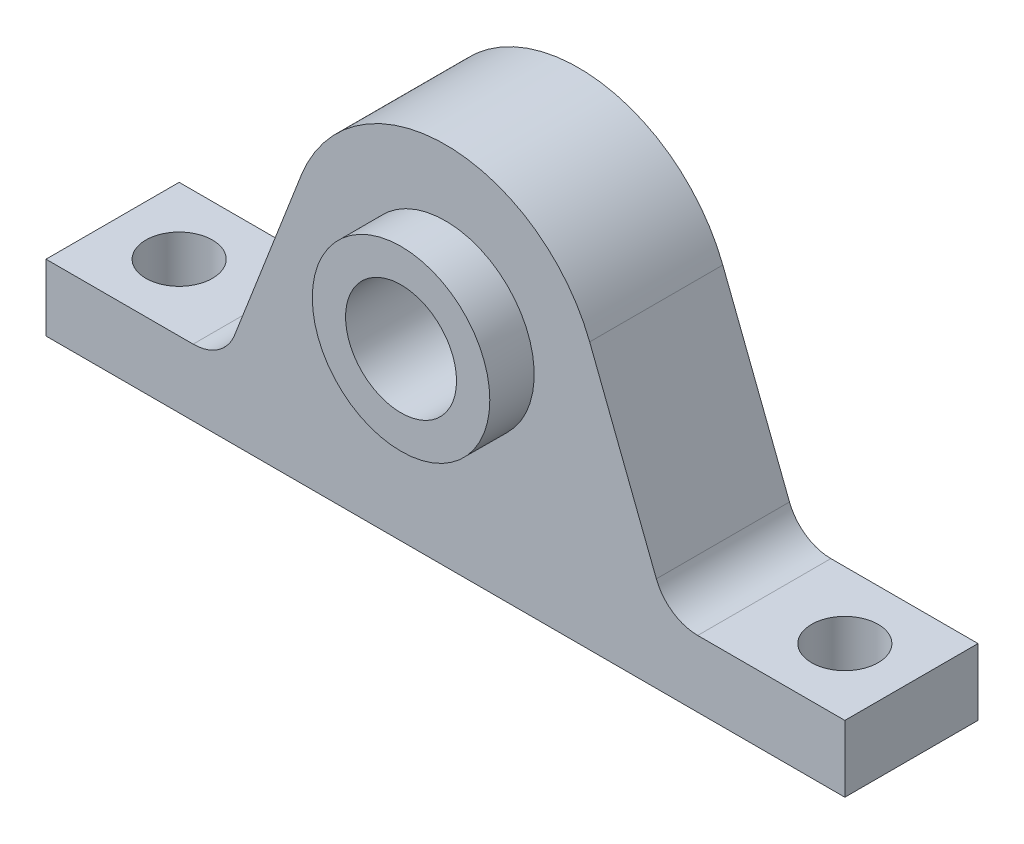
SolidWorks part; units mm, degrees
ref_plane "Front" through (0, 0, 0) normal (0, 0, 1) x (1, 0, 0)
ref_plane "Top" through (0, 0, 0) normal (0, 1, 0) x (1, 0, 0)
ref_plane "Right" through (0, 0, 0) normal (1, 0, 0) x (0, 0, -1)
sketch "Sketch1" plane through (0, 0, 0) normal (0, 0, 1) x (1, 0, 0)
  line L0 (-57.15, 0) -> (57.15, 0)
  line L1 (57.15, 0) -> (57.15, 9.525)
  line L2 (57.15, 9.525) -> (31.75, 9.525)
  line L3 (31.75, 9.525) -> (20.6375, 38.1689)
  line L4 (-57.15, 0) -> (-57.15, 9.525)
  line L5 (-57.15, 9.525) -> (-31.75, 9.525)
  line L6 (-31.75, 9.525) -> (-20.6375, 38.1689)
  line L7 (0, 30.1625) -> (0, 0) construction
  arc A0 (-20.6375, 38.1689) -> (20.6375, 38.1689) centre (0, 30.1625) cw
  dimension "D1" = 41.275
  dimension "D2" = 30.1625
  dimension "D3" = 9.525
  dimension "D4" = 63.5
  dimension "D5" = 114.3
extrude "Extrude1" add sketch "Sketch1" along normal mid plane 19.05
fillet "Fillet1" radius 6.35 2 edges at (-31.75, 9.525, 0) (31.75, 9.525, 0)
sketch "Sketch2" plane through (0, 0, 0) normal (0, 0, 1) x (1, 0, 0)
  circle A0 centre (0, 30.1625) radius 12.7
  arc A1 (20.6375, 38.1689) -> (-20.6375, 38.1689) centre (0, 30.1625) ccw construction
  dimension "D1" = 25.4
extrude "Extrude2" add sketch "Sketch2" along normal mid plane 31.75
sketch "Sketch3" plane through (0, 0, 15.875) normal (0, 0, 1) x (1, 0, 0)
  circle A0 centre (0, 30.1625) radius 7.9375
  circle A1 centre (0, 30.1625) radius 12.7 construction
  dimension "D1" = 15.875
extrude "Cut-Extrude1" cut sketch "Sketch3" against normal through all
sketch "Sketch4" plane through (0, 9.525, 0) normal (0, 1, 0) x (-1, 0, 0)
  line L0 (0, -15.875) -> (0, 15.875) construction
  line L1 (-12.7, -15.875) -> (12.7, -15.875) construction
  line L2 (12.7, 15.875) -> (-12.7, 15.875) construction
  circle A0 centre (-47.625, 0) radius 4.7625
  circle A1 centre (47.625, 0) radius 4.7625
  dimension "D1" = 9.525
  dimension "D2" = 95.25
extrude "Cut-Extrude2" cut sketch "Sketch4" against normal through all
